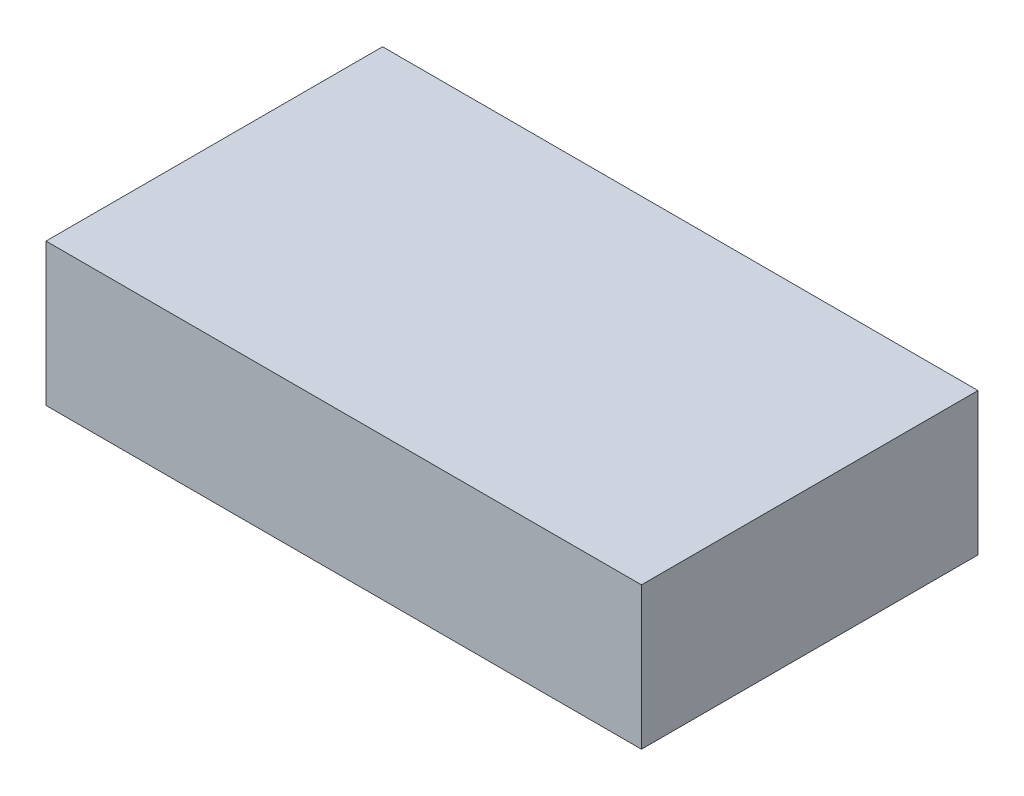
SolidWorks part; units mm, degrees
ref_plane "Front Plane" through (0, 0, 0) normal (0, 0, 1) x (1, 0, 0)
ref_plane "Top Plane" through (0, 0, 0) normal (0, 1, 0) x (1, 0, 0)
ref_plane "Right Plane" through (0, 0, 0) normal (1, 0, 0) x (0, 0, -1)
sketch "Sketch1" plane through (0, 0, 0) normal (0, 1, 0) x (1, 0, 0)
  line L1 (-23, 13) -> (23, 13)
  line L2 (-23, 13) -> (-23, -13)
  line L3 (-23, -13) -> (23, -13)
  line L4 (23, 13) -> (23, -13)
  point P4 (0, -13)
  point P6 (-23, 0)
  dimension "D1" = 46
  dimension "D2" = 26
extrude "Boss-Extrude1" add sketch "Sketch1" along normal blind 11
sketch "Sketch2" plane through (0, 11, 0) normal (0, 1, 0) x (1, 0, 0)
  line L0 (-23, 0) -> (23, 0)
  line L1 (-23, 13) -> (-23, -13) construction
  line L2 (23, -13) -> (23, 13) construction
  text T0 "WEAPON ESC"
  point P2 (-23, 0)
  point P5 (23, 0)
